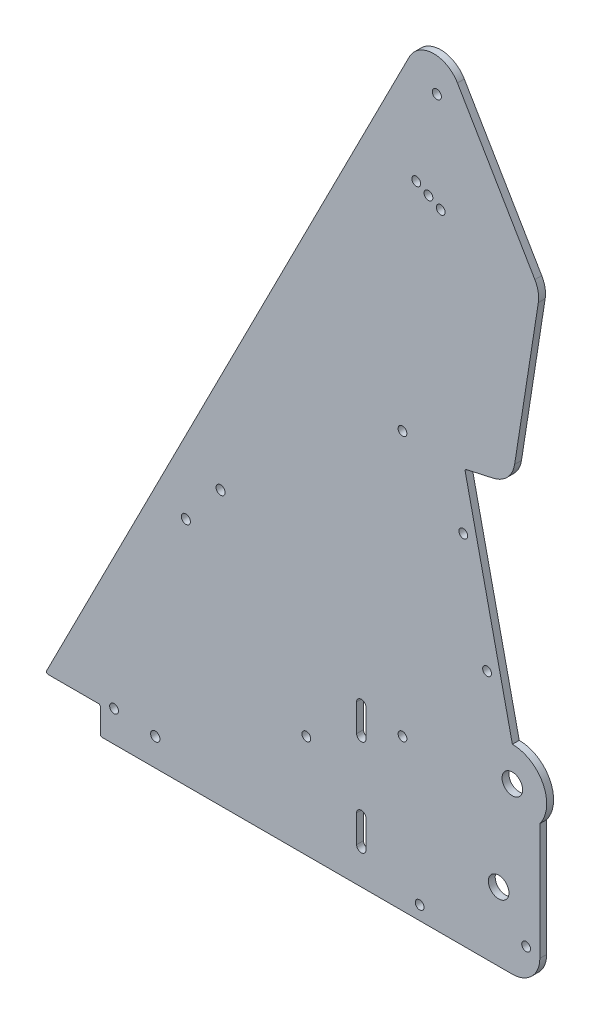
SolidWorks part; units mm, degrees
other "Markup1"
sketch "Sketch5"
ref_plane "Front Plane" through (0, 0, 0) normal (0, 0, 1) x (1, 0, 0)
ref_plane "Top Plane" through (0, 0, 0) normal (0, 1, 0) x (1, 0, 0)
ref_plane "Right Plane" through (0, 0, 0) normal (1, 0, 0) x (0, 0, -1)
sketch "Sketch1" plane through (0, 0, 0) normal (0, 0, 1) x (1, 0, 0)
  line L1 (228.6, -12.7) -> (228.6, 53.975)
  line L2 (178.7547, 351.4131) -> (0, 0)
  line L3 (228.6, 266.7) -> (178.7547, 351.4131)
  line L5 (0, 0) -> (25.4, 0)
  line L6 (25.4, 0) -> (25.4, -12.7)
  line L7 (25.4, -12.7) -> (228.6, -12.7)
  line L9 (215.9, 79.375) -> (193.9097, 178.5667)
  line L10 (193.9097, 178.5667) -> (215.6079, 183.377)
  line L11 (215.6079, 183.377) -> (228.6, 266.7)
  arc A0 (228.6, 53.975) -> (215.9, 79.375) centre (215.9, 63.5) ccw
  dimension "D7" = 12.7
  dimension "D8" = 76.2
  dimension "D10" = 31.75
  dimension "D2" = 279.4
  dimension "D3" = 25.4
  dimension "D4" = 215.9
  dimension "D5" = 394.2644
  dimension "D6" = 203.2
  dimension "D9" = 63.039
  dimension "D11" = 101.6
  dimension "D12" = 12.5
  dimension "D13" = 22.225
extrude "Boss-Extrude1" add sketch "Sketch1" along normal blind 3.175
sketch "Sketch2" plane through (0, 0, 3.175) normal (0, 0, 1) x (1, 0, 0)
  line L0 (178.7547, 351.4131) -> (0, 0) construction
  line L1 (25.4, -12.7) -> (228.6, -12.7) construction
  line L2 (215.9, 79.375) -> (193.9097, 178.5667) construction
  line L3 (193.9097, 178.5667) -> (215.6079, 183.377) construction
  line L4 (215.9, 79.375) -> (193.9097, 178.5667) construction
  line L10 (228.6, -12.7) -> (228.6, 53.975) construction
  circle A0 centre (64.9432, 94.0578) radius 2.0955
  circle A1 centre (180.975, 322.1643) radius 2.0955
  circle A2 centre (81.0071, 113.733) radius 2.0955
  circle A3 centre (193.2078, 152.3944) radius 2.032
  circle A4 centre (215.9, 63.5) radius 4.7625
  circle A7 centre (173.0375, -6.35) radius 2.032
  circle A8 centre (204.203, 102.7985) radius 2.032
  circle A26 centre (209.55, 19.05) radius 4.7625
  arc A30 (228.6, 53.975) -> (215.9, 79.375) centre (215.9, 63.5) ccw construction
  circle A31 centre (165.1, 179.3875) radius 2.032
  circle A32 centre (182.7697, 276.817) radius 2.032 construction
  circle A33 centre (177.1098, 279.696) radius 2.032 construction
  circle A34 centre (171.45, 282.575) radius 2.032 construction
  circle A35 centre (182.7697, 276.817) radius 2.032
  circle A36 centre (177.1098, 279.696) radius 2.032
  circle A37 centre (171.45, 282.575) radius 2.032
  dimension "D3" = 4.191
  dimension "D5" = 4.191
  dimension "D9" = 4.191
  dimension "D20" = 9.525
  dimension "D23" = 9.525
  dimension "D18" = 4.064
  dimension "D26" = 4.064
  dimension "D14" = 4.064
  dimension "D2" = 15.24
  dimension "D6" = 15.24
  dimension "D7" = 25.4
  dimension "D8" = 20.6375
  dimension "D21" = 44.45
  dimension "D22" = 6.35
  dimension "D19" = 160.3375
  dimension "D24" = 44.45
  dimension "D25" = 6.35
  dimension "D27" = 25.4
  dimension "D28" = 50.8
  dimension "D29" = 6.35
  dimension "D17" = 6.35
  dimension "D33" = 55.5625
  dimension "D15" = 114.3
  dimension "D4" = 180.975
extrude "Cut-Extrude1" cut sketch "Sketch2" against normal through all
sketch "Sketch7" plane through (0, 0, 3.175) normal (0, 0, 1) x (1, 0, 0)
  line L0 (146.05, 3.175) -> (146.05, 15.875) construction
  line L1 (143.891, 3.175) -> (143.891, 15.875)
  line L2 (148.209, 3.175) -> (148.209, 15.875)
  line L3 (146.05, 47.625) -> (146.05, 60.325) construction
  line L4 (143.891, 47.625) -> (143.891, 60.325)
  line L5 (148.209, 47.625) -> (148.209, 60.325)
  line L6 (25.4, -12.7) -> (228.6, -12.7) construction
  line L12 (228.6, -12.7) -> (228.6, 53.975) construction
  line L13 (25.4, -12.7) -> (228.6, -12.7) construction
  arc A0 (143.891, 3.175) -> (148.209, 3.175) centre (146.05, 3.175) ccw
  arc A1 (148.209, 15.875) -> (143.891, 15.875) centre (146.05, 15.875) ccw
  arc A2 (143.891, 47.625) -> (148.209, 47.625) centre (146.05, 47.625) ccw
  arc A3 (148.209, 60.325) -> (143.891, 60.325) centre (146.05, 60.325) ccw
  circle A8 centre (50.8, 0) radius 2.159
  point P2 (146.05, 9.525)
  point P9 (146.05, 53.975)
  dimension "D1" = 4.318
  dimension "D5" = 4.318
  dimension "D2" = 12.7
  dimension "D3" = 12.7
  dimension "D4" = 44.45
  dimension "D6" = 95.25
  dimension "D7" = 82.55
  dimension "D8" = 15.875
  dimension "D9" = 12.7
extrude "Cut-Extrude2" cut sketch "Sketch7" against normal through all
sketch "Sketch10" plane through (0, 0, 3.175) normal (0, 0, 1) x (1, 0, 0)
  circle A1 centre (165.1, 57.15) radius 2.032
  circle A2 centre (120.65, 34.925) radius 2.032
  dimension "D1" = 4.064
  dimension "D4" = 63.5
  dimension "D5" = 69.85
extrude "Cut-Extrude3" cut sketch "Sketch10" against normal up to next
fillet "Fillet1" radius 12.7 4 edges at (228.6, -12.7, 1.5875) (178.7547, 351.4131, 1.5875) (215.6079, 183.377, 1.5875) (228.6, 266.7, 1.5875)
fillet "Fillet2" radius 0.7937 4 edges at (25.4, -12.7, 1.5875) (25.4, 0, 1.5875) (193.9097, 178.5667, 1.5875) (0, 0, 1.5875)
sketch "Sketch12" plane through (0, 0, 3.175) normal (0, 0, 1) x (1, 0, 0)
  circle A0 centre (31.75, 1.5875) radius 2.032
  circle A1 centre (222.25, 1.5875) radius 2.032
  dimension "D1" = 4.064
extrude "Cut-Extrude5" cut sketch "Sketch12" against normal through all
equation "\"D6@Sketch2\"=\"D2@Sketch2\""
